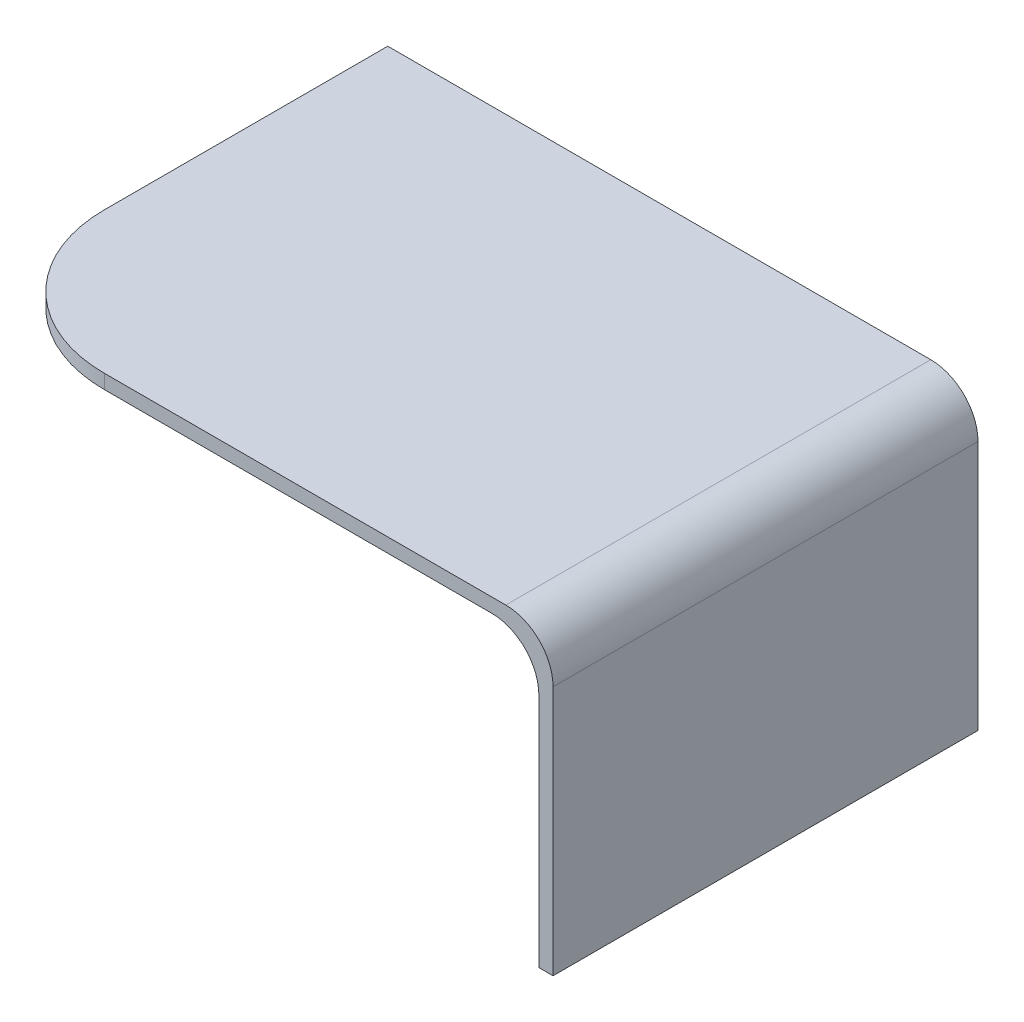
SolidWorks part; units mm, degrees
ref_plane "Front Plane" through (0, 0, 0) normal (0, 0, 1) x (1, 0, 0)
ref_plane "Top Plane" through (0, 0, 0) normal (0, 1, 0) x (1, 0, 0)
ref_plane "Right Plane" through (0, 0, 0) normal (1, 0, 0) x (0, 0, -1)
sketch "Sketch2" plane through (0, 0, 0) normal (0, 0, 1) x (1, 0, 0)
  line L0 (0, 4.05) -> (2.5, 4.05)
  line L1 (0, -4.05) -> (10.5, -4.05)
  line L2 (2.5, 4.05) -> (2.5, 30.95)
  line L3 (2.5, 30.95) -> (-49.5, 30.95)
  line L4 (-49.5, 30.95) -> (-49.5, 33.95)
  line L5 (-49.5, 33.95) -> (10.5, 33.95)
  line L6 (10.5, 33.95) -> (10.5, -4.05)
  line L7 (2.5, 30.95) -> (10.5, 30.95)
  line L8 (10.5, 33.95) -> (65.5, 33.95)
  line L9 (75.5, 23.95) -> (75.5, -29.05)
  line L10 (75.5, -29.05) -> (10.5, -29.05)
  line L11 (10.5, -29.05) -> (10.5, -4.05)
  line L12 (10.5, 30.95) -> (62.5, 30.95)
  line L13 (30.5, 33.95) -> (30.5, 30.95)
  line L14 (72.5, 20.95) -> (72.5, -29.05)
  arc A0 (65.5, 33.95) -> (75.5, 23.95) centre (65.5, 23.95) cw
  arc A1 (62.5, 30.95) -> (72.5, 20.95) centre (62.5, 20.95) cw
  point P4 (0, 0)
  line B0 (0, -7.95) -> (-2.04, -7.95)
  line B1 (-6.1524, -4.048) -> (-6.1524, 4.048)
  line B2 (-2.04, 7.95) -> (0, 7.95)
  line B3 (0, 7.95) -> (0, -7.95)
  line B4 (-2.04, -7.95) -> (-6.1524, -4.048)
  line B5 (-6.1524, 4.048) -> (-2.04, 7.95)
  line B6 (0, -4.05) -> (0, 4.05) construction
  dimension "D10" = 10
  dimension "D1" = 10.5
  dimension "D2" = 8
  dimension "D3" = 3
  dimension "D4" = 60
  dimension "D5" = 35
  dimension "D6" = 65
  dimension "D7" = 60
  dimension "D8" = 20
  dimension "D9" = 3
sketch_block_instance "Extrusion Profile-1"
sketch_block "Block1" parameters "D1"=8.44, "D2"=2.6, "D3"=6, "D4"=16.7, "D6"=5.6686, "D7"=2.0404, "D8"=8.0963, "D9"=15.9, "D5"=2.4157
extrude "Boss-Extrude1" add sketch "Sketch2" along normal blind 6 contours L0 B3 L1 L6 L7 L2 | B2 B5 B1 B4 B0 B3 region at (-2.7416, 0, 0) region at (6.1459, 12.5429, 0)
extrude "Boss-Extrude2" add sketch "Sketch2<3>" along normal blind 90 contours L3 L7 L6 L5 L4 | L13 L8 L6 | L12 A1 L14 L10 L9 A0 L8 L13 region at (-19.5, 32.45, 0) region at (20.5, 32.45, 0) region at (31.2742, 32.45, 0)
sketch "Sketch2<3>" plane through (0, 0, 0) normal (0, 0, 1) x (1, 0, 0) same geometry as "Sketch2"
extrude "Boss-Extrude3" add sketch "Sketch2<4>" along normal blind 3 contours L6 L11 L10 L9 | L8 L13 L9 region at (41.3331, 0.7889, 0) region at (31.2742, 32.45, 0)
sketch "Sketch2<4>" plane through (0, 0, 0) normal (0, 0, 1) x (1, 0, 0) same geometry as "Sketch2"
fillet "Fillet1" radius 3 1 edges at (10.5, 13.45, 3)
fillet "Fillet2" radius 3 1 edges at (10.5, 13.45, 6)
fillet "Fillet3" radius 30 1 edges at (-49.5, 32.45, 90)
sketch "Sketch3" plane through (0, 0, 0) normal (0, 0, -1) x (-1, 0, 0)
  line L0 (-2.5, 4.05) -> (-2.5, -4.05)
  line L1 (0, -4.05) -> (-10.5, -4.05) construction
  line L18 (49.5, 33.95) -> (-65.5, 33.95)
  line L19 (-75.5, 23.95) -> (-75.5, -29.05)
  line L20 (-75.5, -29.05) -> (-10.5, -29.05)
  line L21 (-10.5, -29.05) -> (-10.5, -4.05)
  line L22 (-10.5, -4.05) -> (0, -4.05)
  line L23 (0, -4.05) -> (0, -7.95)
  line L24 (0, -7.95) -> (2.04, -7.95)
  line L25 (2.04, -7.95) -> (6.1524, -4.048)
  line L26 (6.1524, -4.048) -> (6.1524, 4.048)
  line L27 (6.1524, 4.048) -> (2.04, 7.95)
  line L28 (2.04, 7.95) -> (0, 7.95)
  line L29 (0, 7.95) -> (0, 4.05)
  line L30 (0, 4.05) -> (-2.5, 4.05)
  line L31 (-2.5, 4.05) -> (-2.5, 30.95)
  line L32 (-2.5, 30.95) -> (49.5, 30.95)
  line L33 (49.5, 30.95) -> (49.5, 33.95)
  line L34 (49.5, 33.95) -> (-65.5, 33.95)
  line L35 (-75.5, 23.95) -> (-75.5, -29.05)
  line L36 (-75.5, -29.05) -> (-10.5, -29.05)
  line L37 (-10.5, -29.05) -> (-10.5, -4.05)
  line L38 (-10.5, -4.05) -> (-2.5, -4.05)
  line L47 (-2.5, 4.05) -> (-2.5, 30.95)
  line L48 (-2.5, 30.95) -> (49.5, 30.95)
  line L49 (49.5, 30.95) -> (49.5, 33.95)
  arc A1 (-65.5, 33.95) -> (-75.5, 23.95) centre (-65.5, 23.95) ccw
  arc A2 (-65.5, 33.95) -> (-75.5, 23.95) centre (-65.5, 23.95) ccw
  dimension "D1" = 0
sketch "Sketch4" plane through (0, 0, 0) normal (0, 0, -1) x (-1, 0, 0)
  line L0 (6.1524, 1) -> (6.1524, -1)
  line L1 (6.1524, -4.048) -> (6.1524, 4.048) construction
  line L2 (6.1524, -1) -> (2.1524, -1)
  line L3 (2.1524, -1) -> (2.1524, 1)
  line L4 (2.1524, 1) -> (6.1524, 1)
  point P5 (6.1524, 0)
  dimension "D1" = 2
  dimension "D2" = 4
extrude "Cut-Extrude1" cut sketch "Sketch4" against normal through all
